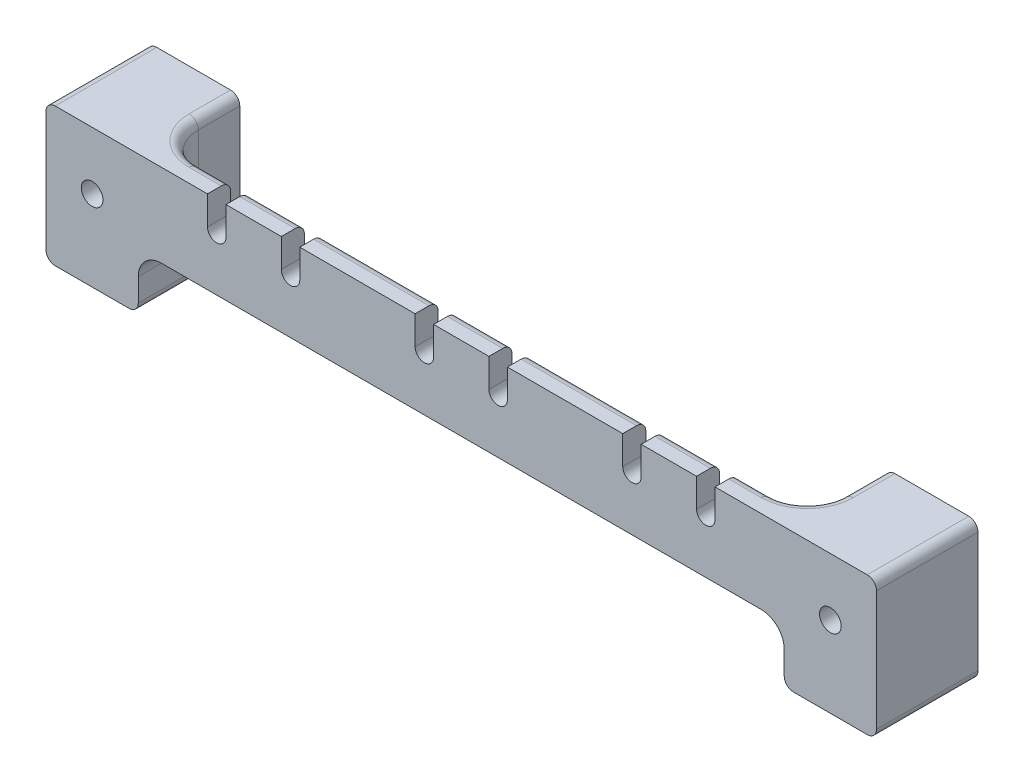
SolidWorks part; units mm, degrees
material "ABS"
ref_plane "Front Plane" through (0, 0, 0) normal (0, 0, 1) x (1, 0, 0)
ref_plane "Top Plane" through (0, 0, 0) normal (0, 1, 0) x (1, 0, 0)
ref_plane "Right Plane" through (0, 0, 0) normal (1, 0, 0) x (0, 0, -1)
sketch "Sketch1" plane through (0, 0, 0) normal (0, 0, 1) x (1, 0, 0)
  line L1 (0, 0) -> (180, 0)
  line L2 (0, 0) -> (0, 30)
  line L3 (0, 30) -> (180, 30)
  line L4 (180, 0) -> (180, 30)
  circle A0 centre (10, 17.5) radius 2.35
  circle A1 centre (170, 17.5) radius 2.35
  dimension "D2" = 4.7
  dimension "D1" = 180
  dimension "D3" = 30
  dimension "D4" = 160
  dimension "D5" = 10
  dimension "D6" = 12.5
extrude "Boss-Extrude1" add sketch "Sketch1" along normal blind 22
sketch "Sketch2" plane through (0, 30, 0) normal (0, 1, 0) x (1, 0, 0)
  line L0 (180, 0) -> (0, 0) construction
  line L1 (160, 0) -> (20, 0)
  line L2 (160, 0) -> (160, -17)
  line L3 (160, -17) -> (20, -17)
  line L4 (20, 0) -> (20, -17)
  line L5 (180, -22) -> (180, 0) construction
  line L6 (0, -22) -> (0, 0) construction
  dimension "D1" = 20
  dimension "D2" = 20
  dimension "D3" = 17
extrude "Cut-Extrude1" cut sketch "Sketch2" against normal blind 30
sketch "Sketch3" plane through (0, 0, 22) normal (0, 0, 1) x (1, 0, 0)
  line L1 (20, 0) -> (160, 0)
  line L2 (20, 0) -> (20, 12)
  line L3 (20, 12) -> (160, 12)
  line L4 (160, 0) -> (160, 12)
  line L5 (0, 30) -> (0, 0) construction
  line L6 (180, 0) -> (180, 30) construction
  line L7 (0, 0) -> (180, 0) construction
  dimension "D1" = 20
  dimension "D2" = 20
  dimension "D3" = 12
extrude "Cut-Extrude2" cut sketch "Sketch3" against normal blind 22
sketch "Sketch4" plane through (0, 0, 22) normal (0, 0, 1) x (1, 0, 0)
  line L3 (143, 23.808) -> (143, 31.808) construction
  line L4 (141, 23.808) -> (141, 31.808)
  line L5 (145, 23.808) -> (145, 31.808)
  line L7 (160, 12) -> (20, 12) construction
  line L8 (180, 0) -> (180, 30) construction
  line L9 (98, 23.808) -> (98, 31.808) construction
  line L10 (96, 23.808) -> (96, 31.808)
  line L11 (100, 23.808) -> (100, 31.808)
  line L12 (53, 23.808) -> (53, 31.808) construction
  line L13 (51, 23.808) -> (51, 31.808)
  line L14 (55, 23.808) -> (55, 31.808)
  line L15 (37, 23.808) -> (37, 31.808) construction
  line L16 (35, 23.808) -> (35, 31.808)
  line L17 (39, 23.808) -> (39, 31.808)
  line L18 (0, 30) -> (0, 0) construction
  line L19 (82, 23.808) -> (82, 31.808) construction
  line L20 (80, 23.808) -> (80, 31.808)
  line L21 (84, 23.808) -> (84, 31.808)
  line L22 (127, 23.808) -> (127, 31.808) construction
  line L23 (125, 23.808) -> (125, 31.808)
  line L24 (129, 23.808) -> (129, 31.808)
  arc A3 (141, 23.808) -> (145, 23.808) centre (143, 23.808) ccw
  arc A4 (145, 31.808) -> (141, 31.808) centre (143, 31.808) ccw
  arc A5 (96, 23.808) -> (100, 23.808) centre (98, 23.808) ccw
  arc A6 (100, 31.808) -> (96, 31.808) centre (98, 31.808) ccw
  arc A7 (51, 23.808) -> (55, 23.808) centre (53, 23.808) ccw
  arc A8 (55, 31.808) -> (51, 31.808) centre (53, 31.808) ccw
  arc A9 (35, 23.808) -> (39, 23.808) centre (37, 23.808) ccw
  arc A10 (39, 31.808) -> (35, 31.808) centre (37, 31.808) ccw
  arc A11 (80, 23.808) -> (84, 23.808) centre (82, 23.808) ccw
  arc A12 (84, 31.808) -> (80, 31.808) centre (82, 31.808) ccw
  arc A13 (125, 23.808) -> (129, 23.808) centre (127, 23.808) ccw
  arc A14 (129, 31.808) -> (125, 31.808) centre (127, 31.808) ccw
  point P7 (143, 27.808)
  point P8 (98, 27.808)
  point P20 (53, 27.808)
  point P27 (37, 27.808)
  point P37 (82, 27.808)
  point P44 (127, 27.808)
  dimension "D1" = 15.808
  dimension "D3" = 4
  dimension "D4" = 8
  dimension "D8" = 8
  dimension "D2" = 37
  dimension "D5" = 3
  dimension "D6" = 45
  dimension "D7" = 37
  dimension "D9" = 4
  dimension "D10" = 15.808
  dimension "D12" = 45
  dimension "D11" = 3
extrude "Cut-Extrude3" cut sketch "Sketch4" against normal blind 48
fillet "Fillet1" radius 8 2 edges at (160, 21, 17) (20, 21, 17)
fillet "Fillet2" radius 5 2 edges at (20, 12, 15.5) (160, 12, 15.5)
fillet "Fillet3" radius 2 5 edges at (158.1848, 10.8545, 14.0742) (153.5281, 12, 16.8527) (90, 12, 17) (26.4719, 12, 16.8527) (21.8152, 10.8545, 14.0742)
fillet "Fillet4" radius 2 17 edges at (20, 30, 4.5) (22.3431, 30, 14.6569) (31.5, 30, 17) (148.5, 30, 17) (157.6569, 30, 14.6569) (160, 30, 4.5) (180, 30, 11) (0, 30, 11) (0, 0, 11) (180, 0, 11) (160, 0, 11) (20, 0, 11) (135, 30, 17) (112.5, 30, 17) (90, 30, 17) (67.5, 30, 17) (45, 30, 17)
